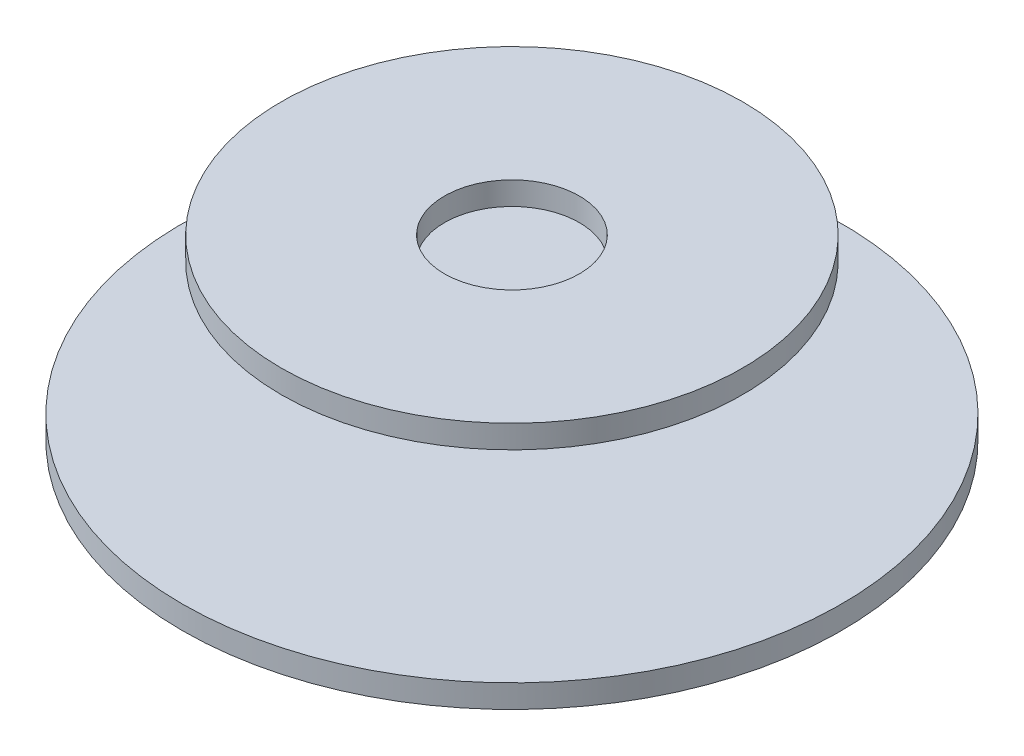
SolidWorks part; units mm, degrees
ref_plane "Front Plane" through (0, 0, 0) normal (0, 0, 1) x (1, 0, 0)
ref_plane "Top Plane" through (0, 0, 0) normal (0, 1, 0) x (1, 0, 0)
ref_plane "Right Plane" through (0, 0, 0) normal (1, 0, 0) x (0, 0, -1)
sketch "Sketch1" plane through (0, 0, 0) normal (0, 1, 0) x (1, 0, 0)
  circle A0 centre (0, 0) radius 127
  dimension "D1" = 254
extrude "Base of base" add sketch "Sketch1" along normal blind 8.89
sketch "Sketch for Supports for Base" plane through (0, 8.89, 0) normal (0, 1, 0) x (1, 0, 0)
  line L0 (0, 0) -> (0, 101.8429) construction
  line L5 (126.7172, 8.4709) -> (107.6672, 8.4709)
  line L7 (-8.4709, 126.7172) -> (-8.4709, 107.6672)
  line L8 (-8.4709, 107.6672) -> (8.4709, 107.6672)
  line L9 (8.4709, 126.7172) -> (8.4709, 107.6672)
  line L10 (107.6672, 8.4709) -> (107.6672, -8.4709)
  line L11 (126.7172, -8.4709) -> (107.6672, -8.4709)
  line L12 (8.4709, -126.7172) -> (8.4709, -107.6672)
  line L13 (8.4709, -107.6672) -> (-8.4709, -107.6672)
  line L14 (-8.4709, -126.7172) -> (-8.4709, -107.6672)
  line L15 (-126.7172, -8.4709) -> (-107.6672, -8.4709)
  line L16 (-107.6672, -8.4709) -> (-107.6672, 8.4709)
  line L17 (-126.7172, 8.4709) -> (-107.6672, 8.4709)
  circle A0 centre (0, 0) radius 127 construction
  circle A1 centre (0, 0) radius 127
  arc A3 (-8.4709, 126.7172) -> (8.4709, 126.7172) centre (0, 0) cw
  arc A4 (126.7172, 8.4709) -> (126.7172, -8.4709) centre (0, 0) cw
  arc A5 (8.4709, -126.7172) -> (-8.4709, -126.7172) centre (0, 0) cw
  arc A6 (-126.7172, -8.4709) -> (-126.7172, 8.4709) centre (0, 0) cw
  point P25 (0, 0)
  dimension "D1" = 16.9418
  dimension "D2" = 19.05
  dimension "D3" = 4
ref_plane "Top Platform Offset" through (0, 59.69, 0) normal (0, 1, 0) x (1, 0, 0)
sketch "Sketch3" plane through (0, 59.69, 0) normal (0, 1, 0) x (1, 0, 0)
  circle A0 centre (0, 0) radius 88.9
  circle A1 centre (0, 0) radius 26
  dimension "D1" = 177.8
  dimension "D2" = 52
extrude "Boss-Extrude2" add sketch "Sketch3" along normal blind 8.89 separate body
